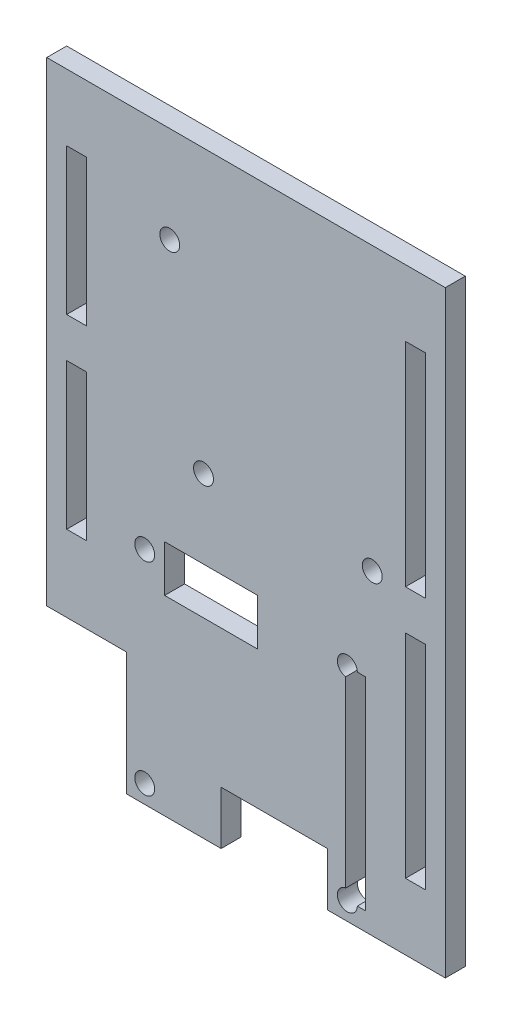
SolidWorks part; units mm, degrees
material "Custom Plastic"
ref_plane "Front Plane" through (0, 0, 0) normal (0, 0, 1) x (1, 0, 0)
ref_plane "Top Plane" through (0, 0, 0) normal (0, 1, 0) x (1, 0, 0)
ref_plane "Right Plane" through (0, 0, 0) normal (1, 0, 0) x (0, 0, -1)
sketch "Sketch1" plane through (0, 0, 0) normal (0, 0, 1) x (1, 0, 0)
  line L1 (-30, 45) -> (30, 45)
  line L2 (-30, 45) -> (-30, -45)
  line L3 (-30, -45) -> (30, -45)
  line L4 (30, 45) -> (30, -45)
  line L5 (-30, 45) -> (30, -45) construction
  line L6 (-30, -45) -> (30, 45) construction
  point P0 (0, 0)
  dimension "D1" = 60
  dimension "D2" = 90
extrude "Boss-Extrude1" add sketch "Sketch1" against normal blind 3
sketch "Sketch3" plane through (0, 0, 0) normal (0, 0, 1) x (1, 0, 0)
  line L0 (30, -45) -> (30, 45) construction
  line L3 (19, 2.56) -> (-6.4, 2.56) construction
  line L4 (30, 45) -> (-30, 45) construction
  circle A0 centre (-11.48, 30.5) radius 1.5
  circle A1 centre (-6.4, 2.56) radius 1.5
  circle A2 centre (19, 2.56) radius 1.5
  dimension "D5" = 3
  dimension "D6" = 3
  dimension "D7" = 3
  dimension "D1" = 27.94
  dimension "D2" = 5.08
  dimension "D3" = 25.4
  dimension "D4" = 14.5
  dimension "D8" = 11
extrude "Cut-Extrude2" cut sketch "Sketch3" against normal blind 3
sketch "Sketch4" plane through (0, 0, 0) normal (0, 0, 1) x (1, 0, 0)
  line L0 (-15.25, -11.75) -> (-15.25, -42.25) construction
  line L1 (-15.25, -42.25) -> (15.25, -42.25) construction
  line L2 (15.25, -42.25) -> (15.25, -11.75) construction
  circle A0 centre (-15.25, -42.25) radius 1.5
  circle A1 centre (-15.25, -11.75) radius 1.5
  circle A2 centre (15.25, -42.25) radius 1.5
  circle A3 centre (15.25, -11.75) radius 1.5
  dimension "D3" = 3
  dimension "D1" = 30.5
  dimension "D2" = 30.5
extrude "Cut-Extrude3" cut sketch "Sketch4" against normal through all
sketch "Sketch5" plane through (0, 0, 0) normal (0, 0, 1) x (1, 0, 0)
  line L0 (30, 45) -> (-30, 45) construction
  line L1 (27, -35) -> (24, -35)
  line L2 (27, -35) -> (27, -3)
  line L3 (27, -3) -> (24, -3)
  line L4 (24, -35) -> (24, -3)
  line L5 (27, 3) -> (24, 3)
  line L6 (27, 3) -> (27, 35)
  line L7 (27, 35) -> (24, 35)
  line L8 (24, 3) -> (24, 35)
  line L10 (30, -45) -> (30, 45) construction
  dimension "D1" = 6
  dimension "D2" = 32
  dimension "D3" = 10
  dimension "D4" = 3
  dimension "D5" = 3
extrude "Cut-Extrude4" cut sketch "Sketch5" against normal through all
sketch "Sketch6" plane through (0, 0, 0) normal (0, 0, 1) x (1, 0, 0)
  line L0 (-30, 45) -> (-30, -45) construction
  line L1 (-24, -15) -> (-27, -15)
  line L2 (-24, -15) -> (-24, 7)
  line L3 (-24, 7) -> (-27, 7)
  line L4 (-27, -15) -> (-27, 7)
  line L5 (-24, 13) -> (-27, 13)
  line L6 (-24, 13) -> (-24, 35)
  line L7 (-24, 35) -> (-27, 35)
  line L8 (-27, 13) -> (-27, 35)
  line L9 (-30, -45) -> (30, -45) construction
  line L10 (30, 45) -> (-30, 45) construction
  dimension "D1" = 3
  dimension "D2" = 3
  dimension "D3" = 30
  dimension "D4" = 6
  dimension "D5" = 10
extrude "Cut-Extrude5" cut sketch "Sketch6" against normal through all
sketch "Sketch7" plane through (0, 0, 0) normal (0, 0, 1) x (1, 0, 0)
  line L0 (16.75, -11.75) -> (13.75, -11.75) construction
  line L1 (18, -42.25) -> (15, -42.25)
  line L2 (18, -42.25) -> (18, -11.75)
  line L3 (18, -11.75) -> (15, -11.75)
  line L4 (15, -42.25) -> (15, -11.75)
  line L5 (16.75, -42.25) -> (13.75, -42.25) construction
  line L6 (-30, -45) -> (30, -45) construction
  line L7 (-12.25, -16.25) -> (1.75, -16.25)
  line L8 (-12.25, -16.25) -> (-12.25, -9.25)
  line L9 (-12.25, -9.25) -> (1.75, -9.25)
  line L10 (1.75, -16.25) -> (1.75, -9.25)
  line L11 (12.25, -45) -> (-3.75, -45)
  line L12 (12.25, -45) -> (12.25, -37)
  line L13 (12.25, -37) -> (-3.75, -37)
  line L14 (-3.75, -45) -> (-3.75, -37)
  circle A0 centre (15.25, -11.75) radius 1.5 construction
  circle A1 centre (15.25, -42.25) radius 1.5 construction
  circle A2 centre (-15.25, -11.75) radius 1.5 construction
  point P17 (15.25, -42.25)
  dimension "D1" = 2.5
  dimension "D2" = 3
  dimension "D3" = 7
  dimension "D4" = 14
  dimension "D5" = 3
  dimension "D6" = 3
  dimension "D7" = 2.75
  dimension "D8" = 8
  dimension "D9" = 16
extrude "Cut-Extrude6" cut sketch "Sketch7" against normal through all
sketch "Sketch8" plane through (0, 0, 0) normal (0, 0, 1) x (1, 0, 0)
  line L0 (-30, -45) -> (-3.75, -45) construction
  line L1 (-18, -45) -> (-30, -45)
  line L2 (-18, -45) -> (-18, -26.5)
  line L3 (-18, -26.5) -> (-30, -26.5)
  line L4 (-30, -45) -> (-30, -26.5)
  line L5 (-30, 45) -> (-30, -45) construction
  dimension "D1" = 12
  dimension "D2" = 18.5
extrude "Cut-Extrude7" cut sketch "Sketch8" against normal through all
